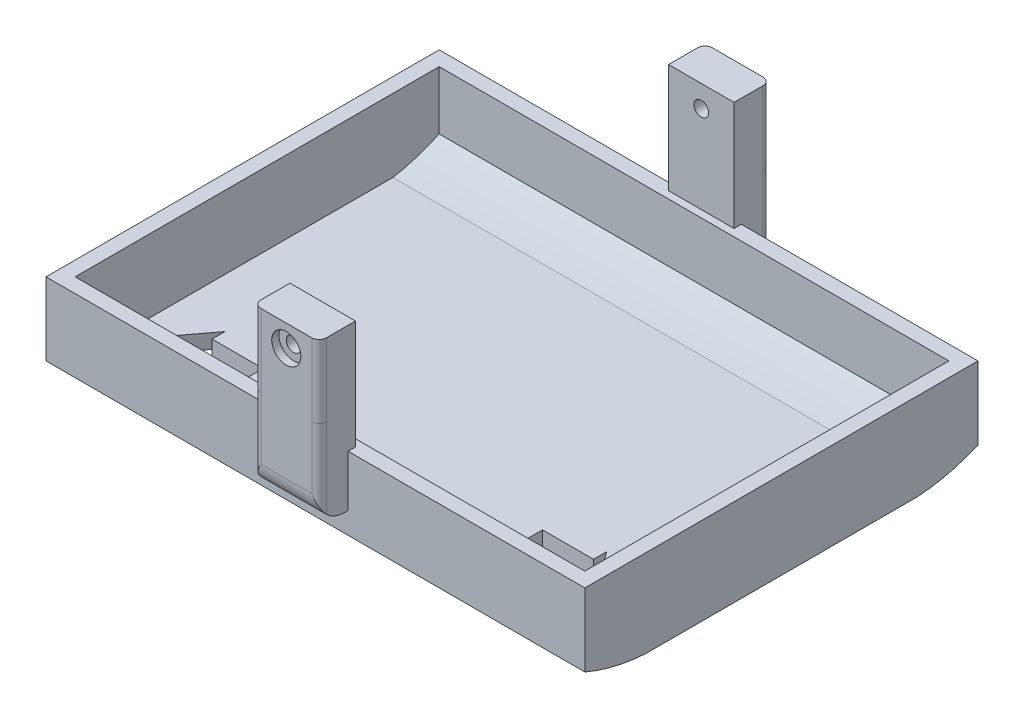
SolidWorks part; units mm, degrees
ref_plane "Alzado" through (0, 0, 0) normal (0, 0, 1) x (1, 0, 0)
ref_plane "Planta" through (0, 0, 0) normal (0, 1, 0) x (1, 0, 0)
ref_plane "Vista lateral" through (0, 0, 0) normal (1, 0, 0) x (0, 0, -1)
sketch "Croquis1" plane through (0, 0, 0) normal (0, 1, 0) x (1, 0, 0)
  line L1 (-37, 27) -> (37, 27)
  line L2 (-37, 27) -> (-37, -27)
  line L3 (-37, -27) -> (37, -27)
  line L4 (37, 27) -> (37, -27)
  line L5 (-37, 27) -> (37, -27) construction
  line L6 (-37, -27) -> (37, 27) construction
  point P0 (0, 0)
extrude "Saliente-Extruir1" add sketch "Croquis1" along normal mid plane 12
sketch "Croquis3" plane through (0, 6, 0) normal (0, 1, 0) x (1, 0, 0)
  line L0 (0, 27) -> (0, -27) construction
  line L1 (37, 27) -> (-37, 27) construction
  line L2 (-37, -27) -> (37, -27) construction
  line L3 (-4.5, -26) -> (4.5, -26)
  line L4 (4.5, -26) -> (4.5, -31)
  line L5 (4.5, -31) -> (-4.5, -31)
  line L6 (-4.5, -31) -> (-4.5, -26)
  line L7 (0, 0) -> (37, 0) construction
  line L8 (37, -27) -> (37, 27) construction
  line L9 (4.5, 31) -> (-4.5, 31)
  line L10 (4.5, 26) -> (4.5, 31)
  line L11 (-4.5, 26) -> (4.5, 26)
  line L12 (-4.5, 31) -> (-4.5, 26)
  point P10 (0, -26)
  dimension "D1" = 9
  dimension "D2" = 5
  dimension "D3" = 1
extrude "Saliente-Extruir2" add sketch "Croquis3" along normal mid plane 20
fillet "Redondeo1" radius 1 4 edges at (-4.5, 6, -31) (4.5, 6, -31) (-4.5, 6, 31) (4.5, 6, 31)
sketch "Croquis5" plane through (37, 0, 0) normal (1, 0, 0) x (0, 0, -1)
  line L0 (0, 0) -> (0, -6) construction
  line L1 (-27, -6) -> (27, -6) construction
  line L2 (0, -6) -> (31, -6) construction
  line L3 (31, -6) -> (31, 0) construction
  line L4 (31, 16) -> (31, -4) construction
  line L5 (31, 0) -> (0, 0) construction
  line L6 (-31, -1.8208) -> (-31, -6)
  line L7 (-31, -6) -> (-18.6428, -6)
  line L8 (31, -1.8208) -> (31, -6)
  line L9 (31, -6) -> (18.6428, -6)
  arc A1 (31, -1.8208) -> (18.6428, -6) centre (17.0894, 18.9517) cw
  arc A2 (-31, -1.8208) -> (-18.6428, -6) centre (-17.0894, 18.9517) ccw
  dimension "D1" = 25
  dimension "D2" = 17.0894
extrude "Cortar-Extruir1" cut sketch "Croquis5" against normal blind 100
sketch "Croquis6" plane through (-37, 0, 0) normal (-1, 0, 0) x (0, 0, 1)
  line L0 (-27, -1) -> (-27, -4)
  line L1 (-27, -4) -> (-27, 6) construction
  line L3 (-31, -1.8208) -> (-31, 16) construction
  line L5 (-27, -4) -> (-31, -4)
  line L7 (0, 0) -> (0, -6) construction
  line L8 (-18.6428, -6) -> (18.6428, -6) construction
  line L16 (-31, 2.4641) -> (-33.4327, 2.4641)
  line L17 (-33.4327, 2.4641) -> (-33.4327, -4)
  line L18 (-33.4327, -4) -> (-31, -4)
  line L19 (27, -1) -> (27, -4)
  line L20 (27, -4) -> (31, -4)
  line L21 (33.4327, -4) -> (31, -4)
  line L22 (33.4327, 2.4641) -> (33.4327, -4)
  line L23 (31, 2.4641) -> (33.4327, 2.4641)
  arc A0 (-27, -1) -> (-31, 2.4641) centre (-27.5, 2.4641) cw
  arc A3 (27, -1) -> (31, 2.4641) centre (27.5, 2.4641) ccw
  dimension "D1" = 3.5
  dimension "D2" = 6.4641
  dimension "D3" = 3
  dimension "D4" = 2.4327
  dimension "D5" = 2.4327
extrude "Cortar-Extruir2" cut sketch "Croquis6" against normal blind 100
ref_plane "Plano2" through (-35, 0, 0) normal (-1, 0, 0) x (0, 0, 1)
sketch "Croquis7" plane through (-35, 0, 0) normal (-1, 0, 0) x (0, 0, 1)
  line L0 (-25, 6) -> (25, 6)
  line L1 (-27, 6) -> (27, 6) construction
  line L3 (-27, -1) -> (-27, 6) construction
  line L4 (0, 0) -> (0, -4) construction
  line L5 (18.6428, -4) -> (-18.6428, -4)
  line L6 (-25, 6) -> (-25, -2)
  line L7 (-18.6428, -6) -> (18.6428, -6) construction
  line L8 (25, 6) -> (25, -2)
  arc A0 (18.6428, -4) -> (25, -2) centre (14.3858, 20.6349) ccw
  arc A2 (-18.6428, -4) -> (-25, -2) centre (-14.3858, 20.6349) cw
  point P11 (-25, -2)
  point P14 (-25, -2)
  point P15 (-18.6428, -4)
  point P16 (-25, -2.0668)
  point P19 (0, 0)
  point P20 (-25, -2.0217)
  point P21 (0, 0)
  dimension "D3" = 25
  dimension "D4" = 18.6428
  dimension "D5" = 8
  dimension "D2" = 2
  dimension "D6" = 2
extrude "Cortar-Extruir3" cut sketch "Croquis7" against normal blind 70
sketch "Croquis8" plane through (0, -6, 0) normal (0, -1, 0) x (1, 0, 0)
  line L0 (0, 0) -> (0, 27) construction
  line L1 (-37, 27) -> (37, 27) construction
  line L2 (-37, 27) -> (-37, -27) construction
  line L3 (-37, -27) -> (37, -27) construction
  line L4 (37, 27) -> (37, -27) construction
  line L5 (-37, 27) -> (37, -27) construction
  line L6 (-37, -27) -> (37, 27) construction
  line L7 (-26.5, 16) -> (22.5, 16) construction
  line L8 (-2, 0) -> (-2, 27) construction
  line L9 (-31.8054, 16) -> (-28.1946, 11.2082)
  line L10 (-28.1946, 11.2082) -> (-28.1946, 13)
  line L11 (-28.1946, 13) -> (-21.1946, 13)
  line L12 (-31.8054, 16) -> (-21.1946, 16) construction
  line L13 (-21.1946, 13) -> (-21.1946, 19)
  line L14 (-28.1946, 20.7918) -> (-28.1946, 19)
  line L15 (-28.1946, 19) -> (-21.1946, 19)
  line L16 (-31.8054, 16) -> (-28.1946, 20.7918)
  line L17 (24.1946, 13) -> (17.1946, 13)
  line L18 (24.1946, 11.2082) -> (24.1946, 13)
  line L19 (27.8054, 16) -> (24.1946, 11.2082)
  line L20 (27.8054, 16) -> (24.1946, 20.7918)
  line L21 (24.1946, 20.7918) -> (24.1946, 19)
  line L22 (24.1946, 19) -> (17.1946, 19)
  line L23 (17.1946, 13) -> (17.1946, 19)
  line L25 (-6, 26) -> (2, 26)
  line L26 (-6, 26) -> (-6, 20)
  line L27 (-6, 20) -> (2, 20)
  line L28 (2, 26) -> (2, 20)
  line L29 (-6, 26) -> (2, 20) construction
  line L30 (-6, 20) -> (2, 26) construction
  point P0 (0, 0)
  point P13 (-2, 16)
  point P19 (-2, 23)
  point P20 (-26.5, 16)
  dimension "D8" = 6
  dimension "D10" = 8
  dimension "D1" = 49
  dimension "D2" = 2
  dimension "D3" = 6
  dimension "D4" = 7
  dimension "D5" = 3
  dimension "D6" = 11
  dimension "D7" = 53
  dimension "D9" = 4
extrude "Cortar-Extruir4" cut sketch "Croquis8" against normal blind 6
fillet "Redondeo2" radius 1 4 edges at (-6, -4.8024, 20) (2, -4.8024, 20) (2, -2.2032, 26) (-6, -2.2032, 26)
sketch "Croquis11" plane through (0, 16, 0) normal (0, 1, 0) x (1, 0, 0)
  line L0 (-4.5, -26) -> (4.5, -26)
  line L1 (4.5, -26) -> (4.5, -31)
  line L2 (4.5, -31) -> (-4.5, -31)
  line L3 (-4.5, -31) -> (-4.5, -26)
  line L6 (4.5, -26) -> (-4.5, -26) construction
  line L7 (-4.5, -26) -> (-4.5, -30) construction
  line L8 (0, 0) -> (34.2137, 0) construction
  line L9 (-4.5, 31) -> (-4.5, 26)
  line L10 (4.5, 31) -> (-4.5, 31)
  line L11 (4.5, 26) -> (4.5, 31)
  line L12 (-4.5, 26) -> (4.5, 26)
  dimension "D1" = 9
  dimension "D2" = 5
extrude "Saliente-Extruir3" add sketch "Croquis11" along normal mid plane 10
fillet "Redondeo3" radius 1 4 edges at (-4.5, 16, -31) (4.5, 16, -31) (-4.5, 16, 31) (4.5, 16, 31)
sketch "Croquis12" plane through (0, 0, 31) normal (0, 0, 1) x (1, 0, 0)
  line L0 (-4.3253, 6) -> (5.8222, 6) construction
  line L1 (-37, 6) -> (-4.5, 6) construction
  line L2 (4.5, 6) -> (37, 6) construction
  line L3 (0, 21) -> (0, 6) construction
  line L4 (-3.5, 21) -> (3.5, 21) construction
  circle A0 centre (0, 18) radius 1
  dimension "D1" = 12
  dimension "D2" = 2
sketch "Croquis17" plane through (0, 0, 31) normal (0, 0, 1) x (1, 0, 0)
  line L0 (-4.5, 6) -> (4.5, 6) construction
  line L1 (0, 6) -> (0, 19) construction
  circle A1 centre (0, 18) radius 1
  point P7 (0, 18)
  dimension "D1" = 1
  dimension "D2" = 13
extrude "Cortar-Extruir10" cut sketch "Croquis17" against normal blind 100
sketch "Croquis18" plane through (0, 0, 31) normal (0, 0, 1) x (1, 0, 0)
  circle A0 centre (0, 18) radius 2
  dimension "D1" = 4
extrude "Cortar-Extruir11" cut sketch "Croquis18" against normal blind 1
sketch "Croquis19" plane through (0, 0, -31) normal (0, 0, -1) x (-1, 0, 0)
  circle A0 centre (0, 18) radius 2
  dimension "D1" = 4
extrude "Cortar-Extruir12" cut sketch "Croquis19" against normal blind 1
extrude "Cortar-Extruir7" cut sketch "Croquis12" against normal blind 100
sketch "Croquis15" plane through (0, 0, 31) normal (0, 0, 1) x (1, 0, 0)
  circle A0 centre (0, 18) radius 2
  dimension "D1" = 4
extrude "Cortar-Extruir8" cut sketch "Croquis15" against normal blind 1
sketch "Croquis16" plane through (0, 0, -31) normal (0, 0, -1) x (-1, 0, 0)
  circle A0 centre (0, 18) radius 2
  dimension "D1" = 4
extrude "Cortar-Extruir9" cut sketch "Croquis16" against normal blind 1
